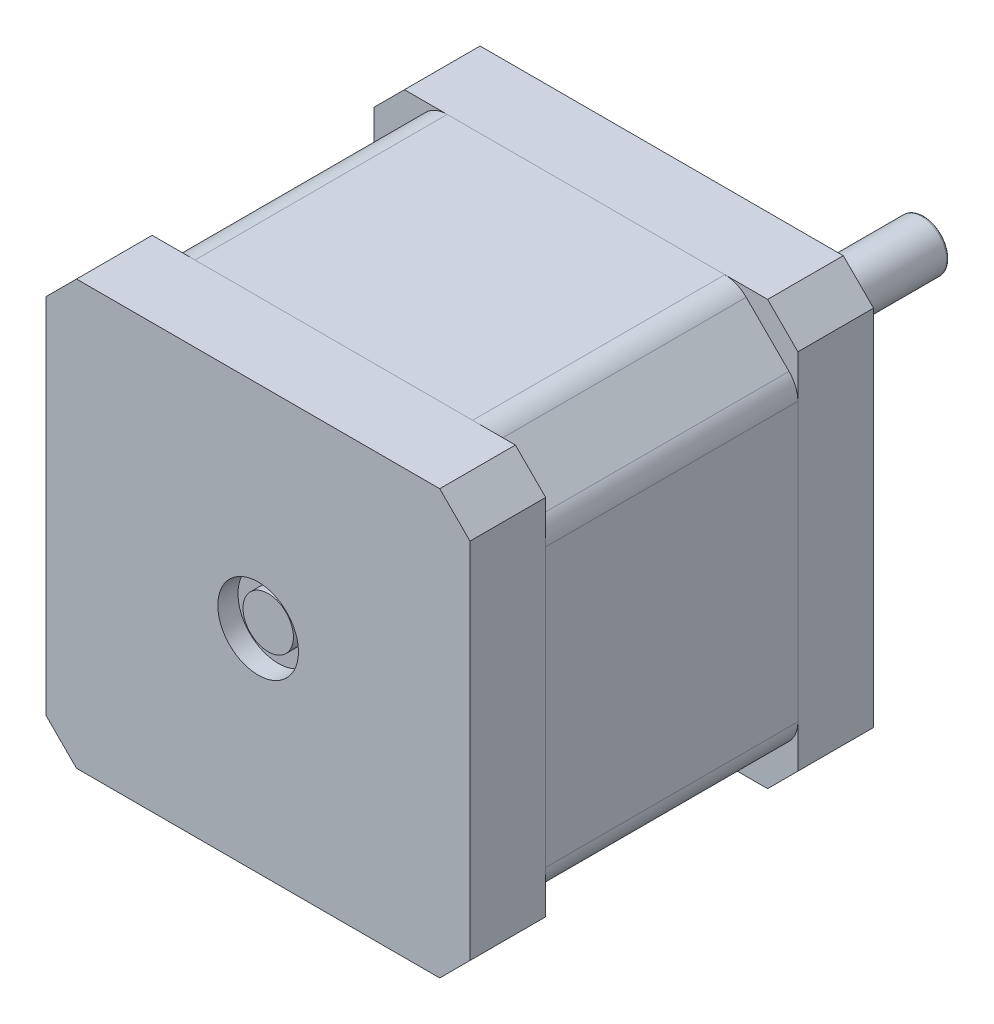
SolidWorks part; units mm, degrees
ref_plane "Ön Düzlem" through (0, 0, 0) normal (0, 0, 1) x (1, 0, 0)
ref_plane "Üst Düzlem" through (0, 0, 0) normal (0, 1, 0) x (1, 0, 0)
ref_plane "Sağ Düzlem" through (0, 0, 0) normal (1, 0, 0) x (0, 0, -1)
sketch "Çizim1" plane through (0, 0, 0) normal (0, 0, 1) x (1, 0, 0)
  line L0 (-15.8783, 20.121) -> (-20.121, 15.8783)
  line L1 (20.121, 15.8783) -> (15.8783, 20.121)
  line L2 (20.121, -15.8783) -> (15.8783, -20.121)
  line L3 (-15.8783, -20.121) -> (-20.121, -15.8783)
  line L4 (13.757, -20.9997) -> (-13.757, -20.9997)
  line L5 (20.9997, -13.757) -> (20.9997, 13.757)
  line L6 (13.757, 20.9997) -> (-13.757, 20.9997)
  line L7 (-20.9997, -13.757) -> (-20.9997, 13.757)
  line L9 (-15.5, -15.5) -> (15.5, -15.5) construction
  line L10 (-15.5, -15.5) -> (-15.5, 15.5) construction
  line L11 (-15.5, 15.5) -> (15.5, 15.5) construction
  line L12 (15.5, -15.5) -> (15.5, 15.5) construction
  line L13 (-15.5, -15.5) -> (15.5, 15.5) construction
  line L14 (-15.5, 15.5) -> (15.5, -15.5) construction
  arc A0 (-20.9997, 13.757) -> (-20.121, 15.8783) centre (-17.9997, 13.757) cw
  arc A1 (-15.8783, 20.121) -> (-13.757, 20.9997) centre (-13.757, 17.9997) cw
  arc A2 (13.757, 20.9997) -> (15.8783, 20.121) centre (13.757, 17.9997) cw
  arc A3 (20.121, 15.8783) -> (20.9997, 13.757) centre (17.9997, 13.757) cw
  arc A4 (20.9997, -13.757) -> (20.121, -15.8783) centre (17.9997, -13.757) cw
  arc A5 (15.8783, -20.121) -> (13.757, -20.9997) centre (13.757, -17.9997) cw
  arc A6 (-13.757, -20.9997) -> (-15.8783, -20.121) centre (-13.757, -17.9997) cw
  arc A7 (-20.121, -15.8783) -> (-20.9997, -13.757) centre (-17.9997, -13.757) cw
  circle A8 centre (-15.5, 15.5) radius 1.5
  circle A9 centre (15.5, 15.5) radius 1.5
  circle A10 centre (15.5, -15.5) radius 1.5
  circle A11 centre (-15.5, -15.5) radius 1.5
  point P6 (0, 0)
  point P28 (0, 20.9997)
  point P29 (0, -20.9997)
  dimension "D1" = 3
  dimension "D2" = 3
  dimension "D3" = 41.9993
  dimension "D7" = 3
  dimension "D8" = 3
  dimension "D9" = 3
  dimension "D10" = 3
  dimension "D4" = 41.9993
  dimension "D5" = 31
  dimension "D6" = 31
extrude "Yükseklik-Ekstrüzyon1" add sketch "Çizim1" along normal blind 25
sketch "Çizim2" plane through (0, 0, 0) normal (0, 0, -1) x (-1, 0, 0)
  line L0 (-21, 18) -> (-18, 21)
  line L1 (-18, -21) -> (18, -21)
  line L2 (-21, -18) -> (-21, 18)
  line L3 (-18, 21) -> (18, 21)
  line L4 (21, -18) -> (21, 18)
  line L5 (-21, -21) -> (21, 21) construction
  line L6 (-21, 21) -> (21, -21) construction
  line L7 (18, 21) -> (21, 18)
  line L8 (18, -21) -> (21, -18)
  line L9 (-21, -18) -> (-18, -21)
  circle A0 centre (-15.5, 15.5) radius 1.5
  circle A1 centre (15.5, 15.5) radius 1.5
  circle A2 centre (15.5, -15.5) radius 1.5
  circle A3 centre (-15.5, -15.5) radius 1.5
  point P0 (0, 0)
  dimension "D1" = 42
  dimension "D2" = 42
extrude "Yükseklik-Ekstrüzyon2" add sketch "Çizim2" along normal blind 7.5
sketch "Çizim3" plane through (0, 0, -7.5) normal (0, 0, -1) x (-1, 0, 0)
  circle A0 centre (0, 0) radius 11
  dimension "D1" = 22
extrude "Yükseklik-Ekstrüzyon3" add sketch "Çizim3" along normal blind 2
fillet "Radyus1" radius 1 1 edges at (11, 0, -7.5)
sketch "Çizim4" plane through (0, 0, -9.5) normal (0, 0, -1) x (-1, 0, 0)
  circle A0 centre (0, 0) radius 4
  dimension "D1" = 8
extrude "Kes-Ekstrüzyon2" cut sketch "Çizim4" against normal blind 2
sketch "Çizim5" plane through (0, 0, -7.5) normal (0, 0, -1) x (-1, 0, 0)
  circle A0 centre (0, 0) radius 2.5
  dimension "D1" = 5
extrude "Yükseklik-Ekstrüzyon4" add sketch "Çizim5" along normal blind 26
sketch "Çizim6" plane through (0, 0, -33.5) normal (0, 0, -1) x (-1, 0, 0)
  line L0 (-2.5, 0) -> (2, 0) construction
  line L1 (2, 2.1161) -> (2, -2.5)
  line L2 (2, -2.5) -> (3.2331, -2.5)
  line L3 (3.2331, -2.5) -> (3.2331, 2.1161)
  line L4 (3.2331, 2.1161) -> (2, 2.1161)
  circle A0 centre (0, 0) radius 2.5 construction
  circle A1 centre (0, 0) radius 2.5 construction
  dimension "D1" = 4.5
extrude "Kes-Ekstrüzyon3" cut sketch "Çizim6" against normal blind 17
fillet "Radyus2" radius 0.25 2 edges at (-2, 0, -33.5) (2.5, 0, -33.5)
sketch "Çizim7" plane through (0, 0, 25) normal (0, 0, 1) x (1, 0, 0)
  line L16 (-18, 21) -> (18, 21)
  line L17 (18, 21) -> (21, 18)
  line L18 (21, 18) -> (21, -18)
  line L19 (21, -18) -> (18, -21)
  line L20 (18, -21) -> (-18, -21)
  line L21 (-18, -21) -> (-21, -18)
  line L22 (-21, -18) -> (-21, 18)
  line L23 (-21, 18) -> (-18, 21)
extrude "Yükseklik-Ekstrüzyon5" add sketch "Çizim7" along normal blind 7.5
sketch "Çizim8" plane through (0, 0, 32.5) normal (0, 0, 1) x (1, 0, 0)
  circle A0 centre (0, 0) radius 4
  dimension "D1" = 8
extrude "Kes-Ekstrüzyon4" cut sketch "Çizim8" against normal blind 2
sketch "Çizim10" plane through (0, 0, 30.5) normal (0, 0, 1) x (1, 0, 0)
  circle A0 centre (0, 0) radius 2.5
  dimension "D1" = 5
extrude "Yükseklik-Ekstrüzyon7" add sketch "Çizim10" along normal blind 1
sketch "Çizim11" plane through (-20.9997, 0, 0) normal (-1, 0, 0) x (0, 0, 1)
  line L0 (12, 0) -> (-12, 0) construction
  line L1 (19, -10) -> (5, -10)
  line L2 (19, -10) -> (19, 10)
  line L3 (19, 10) -> (5, 10)
  line L4 (5, -10) -> (5, 10)
  line L5 (19, -10) -> (5, 10) construction
  line L6 (19, 10) -> (5, -10) construction
  line L7 (25, 13.757) -> (25, -13.757) construction
  point P0 (12, 0)
  dimension "D1" = 14
  dimension "D2" = 20
  dimension "D3" = 6
split line "Ayrım Çizgisi2"
sketch "Çizim12" plane through (-20.9997, 0, 0) normal (-1, 0, 0) x (0, 0, 1)
  line L0 (7.6653, -10) -> (7.6653, 10) construction
  line L1 (5, -10) -> (19, -10) construction
  line L2 (19, 10) -> (5, 10) construction
  text T0 "STEPPING MOTOR\r\nModel No: 17HS4401\r\nLot No:2017411\r\n17A  0.42N.M" font "Century Gothic" height in points 5
extrude "Yükseklik-Ekstrüzyon8" add sketch "Çizim12" along normal blind 0.1
